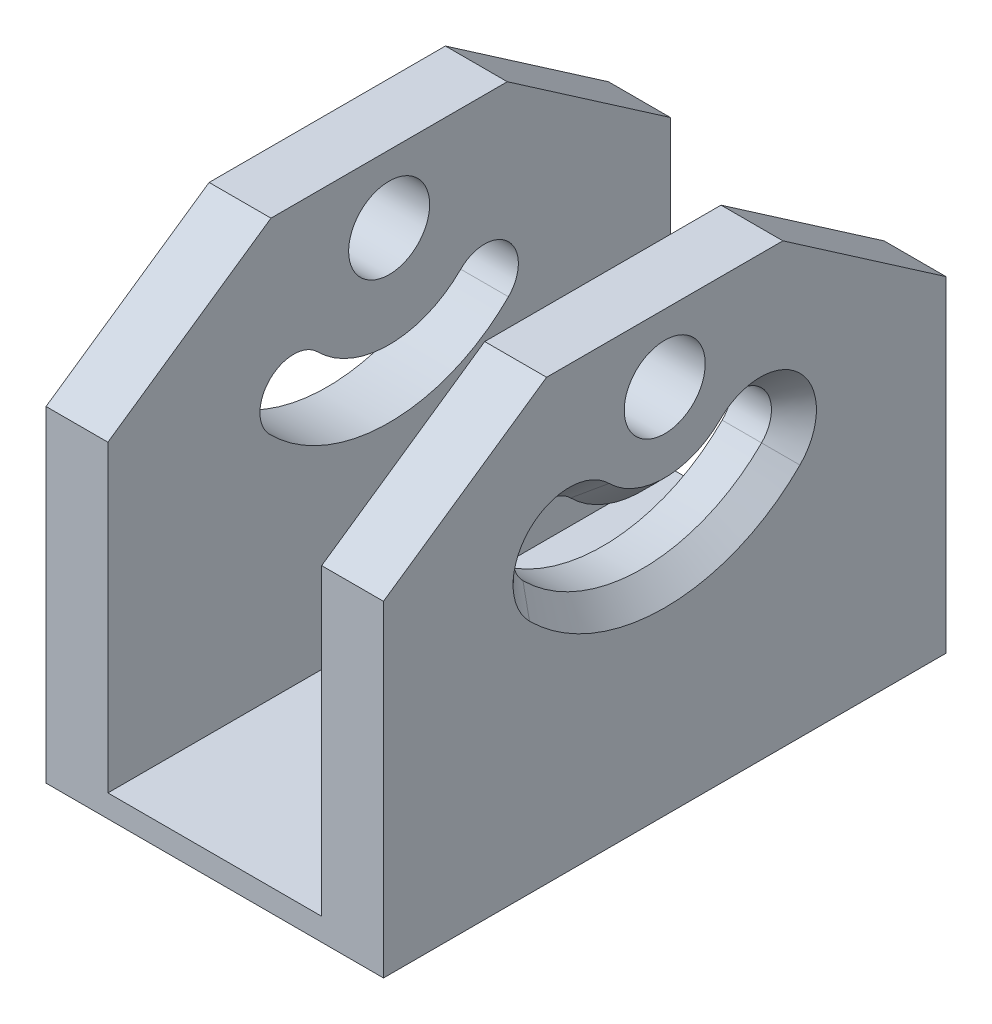
SolidWorks part; units mm, degrees
ref_plane "Front Plane" through (0, 0, 0) normal (0, 0, 1) x (1, 0, 0)
ref_plane "Top Plane" through (0, 0, 0) normal (0, 1, 0) x (1, 0, 0)
ref_plane "Right Plane" through (0, 0, 0) normal (1, 0, 0) x (0, 0, -1)
sketch "Sketch1" plane through (0, 0, 0) normal (1, 0, 0) x (0, 0, -1)
  line L6 (-125, -72.5) -> (125, -72.5)
  line L9 (-125, -72.5) -> (-125, 72.5)
  line L11 (125, -72.5) -> (125, 72.5)
  line L12 (-125, -72.5) -> (125, 72.5) construction
  line L13 (-125, 72.5) -> (125, -72.5) construction
  line L17 (125, 72.5) -> (52.5149, 122.5)
  line L18 (-52.5149, 122.5) -> (-125, 72.5)
  line L19 (0, 122.5) -> (0, 72.5) construction
  line L20 (-52.5149, 122.5) -> (52.5149, 122.5)
  line L21 (-125, 72.5) -> (125, 72.5) construction
  point P0 (0, 0)
  point P1 (0, 0)
  point P8 (0, 67.5)
  dimension "D1" = 250
  dimension "D2" = 145
  dimension "D3" = 50
extrude "Boss-Extrude1" add sketch "Sketch1" along normal blind 150
sketch "Sketch2" plane through (0, 0, 125) normal (0, 0, 1) x (1, 0, 0)
  line L6 (27.5, 122.5) -> (122.5, 122.5)
  line L7 (27.5, 122.5) -> (27.5, -62.5)
  line L8 (27.5, -62.5) -> (122.5, -62.5)
  line L9 (122.5, 122.5) -> (122.5, -62.5)
  line L16 (75, 122.5) -> (75, -62.5) construction
  line L18 (150, 122.5) -> (0, 122.5) construction
  line L19 (150, 72.5) -> (0, 72.5) construction
  point P0 (95, 61.9259)
  point P11 (75, 72.5)
  dimension "D1" = 185
  dimension "D2" = 0
  dimension "D3" = 95
  dimension "D4" = 0
extrude "Cut-Extrude1" cut sketch "Sketch2" against normal blind 250
sketch "Sketch4" plane through (150, 0, 0) normal (1, 0, 0) x (0, 0, -1)
  line L0 (52.5149, 122.5) -> (-52.5149, 122.5) construction
  circle A0 centre (0, 92.5) radius 18
  dimension "D1" = 36
  dimension "D2" = 30
extrude "Cut-Extrude3" cut sketch "Sketch4" against normal blind 250
sketch "Sketch3" plane through (150, 0, 0) normal (1, 0, 0) x (0, 0, -1)
  circle A0 centre (0, 92.5) radius 18 construction
  arc A2 (42.4264, 50.0736) -> (-42.4264, 50.0736) centre (0, 92.5) cw construction
  arc A7 (-53.033, 39.467) -> (53.033, 39.467) centre (0, 92.5) ccw
  arc A8 (-31.8198, 60.6802) -> (31.8198, 60.6802) centre (0, 92.5) ccw
  arc A9 (-31.8198, 60.6802) -> (-53.033, 39.467) centre (-42.4264, 50.0736) ccw
  arc A10 (53.033, 39.467) -> (31.8198, 60.6802) centre (42.4264, 50.0736) ccw
  point P0 (0, 0)
  point P1 (0, 32.5)
  point P6 (0, 32.5)
  point P11 (0, 0)
  point P12 (0, 31.5493)
  point P13 (0, 0)
  point P14 (0, 0)
  point P15 (0, 94.7006)
  dimension "D2" = 30
  dimension "D3" = 60
  dimension "D4" = 0
extrude "Cut-Extrude2" cut sketch "Sketch3" against normal through all
chamfer "Chamfer1" distance 10 angle 45 4 edges at (150, 17.5, 0) (150, 60.6802, -53.033) (150, 47.5, 0) (150, 60.6802, 53.033)
